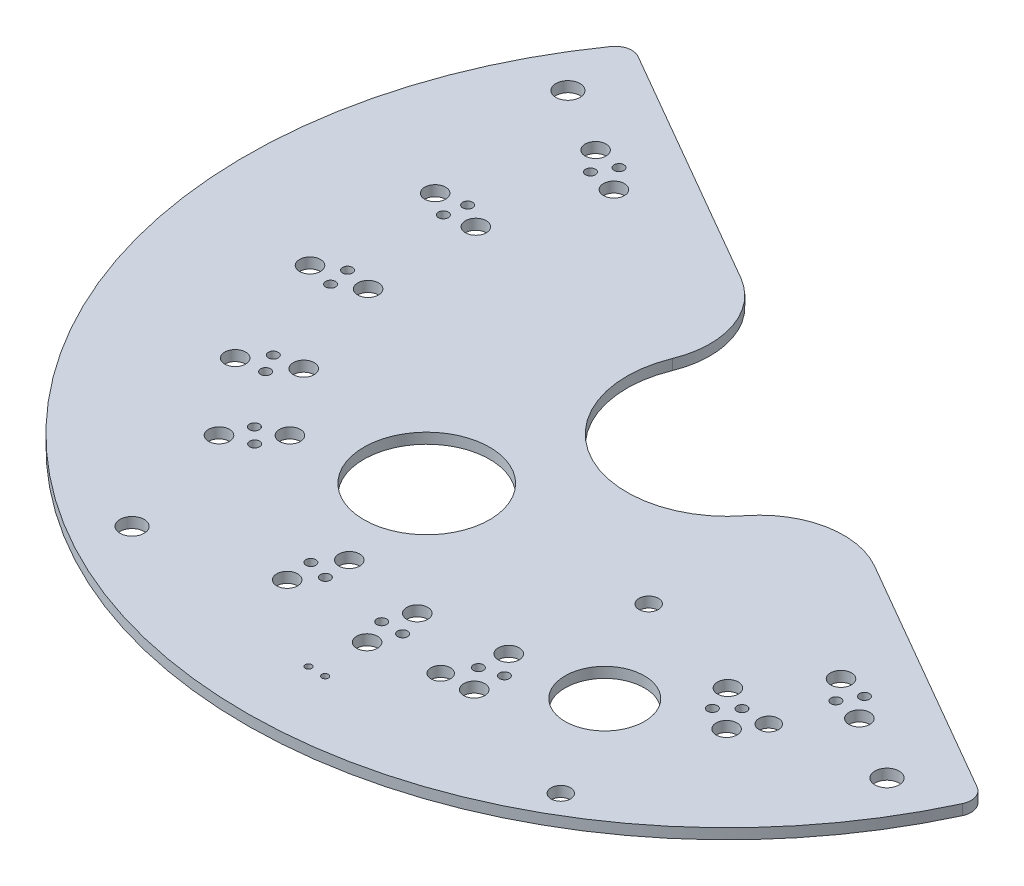
SolidWorks part; units mm, degrees
ref_plane "Front Plane" through (0, 0, 0) normal (0, 0, 1) x (1, 0, 0)
ref_plane "Top Plane" through (0, 0, 0) normal (0, 1, 0) x (1, 0, 0)
ref_plane "Right Plane" through (0, 0, 0) normal (1, 0, 0) x (0, 0, -1)
sketch "Sketch1" plane through (0, 0, 0) normal (0, 1, 0) x (1, 0, 0)
  line L0 (0, 50.8) -> (0, 59.6199) construction
  line L1 (0, 50.8) -> (11.3081, 50.8) construction
  line L2 (0, 0) -> (0, 47) construction
  line L3 (0, 0) -> (-46.286, 8.1615) construction
  line L4 (0, 0) -> (0, 47) construction
  line L5 (0, 0) -> (-46.286, -8.1615) construction
  line L6 (-35.6665, -35.9809) -> (-43.3836, -40.2586) construction
  line L7 (-13.202, -48.8223) -> (-8.5263, -41.3397) construction
  line L8 (34.9566, -37.7798) -> (30.8142, -29.9892) construction
  line L9 (12.3219, -50.1988) -> (12.3219, -41.3754) construction
  circle A0 centre (0, 0) radius 50.8 construction
  circle A1 centre (0, 0) radius 15.24
  circle A2 centre (0, 0) radius 73.025
  circle A3 centre (0, 50.8) radius 6.3 construction
  circle A4 centre (25.4, 43.9941) radius 6.3 construction
  circle A5 centre (43.9941, 25.4) radius 6.3 construction
  circle A6 centre (50.8, 0) radius 6.3 construction
  circle A7 centre (43.9941, -25.4) radius 6.3 construction
  circle A8 centre (25.4, -43.9941) radius 6.3 construction
  circle A9 centre (0, -50.8) radius 6.3 construction
  circle A10 centre (-25.4, -43.9941) radius 6.3 construction
  circle A11 centre (-43.9941, -25.4) radius 6.3 construction
  circle A12 centre (-50.8, 0) radius 6.3 construction
  circle A13 centre (-43.9941, 25.4) radius 6.3 construction
  circle A14 centre (-25.4, 43.9941) radius 6.3 construction
  circle A15 centre (0, 50.8) radius 1.585 construction
  circle A16 centre (-1.585, 50.8) radius 0.75
  circle A17 centre (1.585, 50.8) radius 0.75
  circle A18 centre (0, 50.8) radius 3.8 construction
  circle A19 centre (0, 54.6) radius 1.585
  circle A20 centre (0, 47) radius 1.585
  circle A21 centre (47.285, 27.3) radius 1.585
  circle A22 centre (43.2016, 26.7727) radius 0.75
  circle A23 centre (44.7866, 24.0273) radius 0.75
  circle A24 centre (40.7032, 23.5) radius 1.585
  circle A25 centre (47.285, -27.3) radius 1.585
  circle A26 centre (44.7866, -24.0273) radius 0.75
  circle A27 centre (43.2016, -26.7727) radius 0.75
  circle A28 centre (40.7032, -23.5) radius 1.585
  circle A29 centre (0, -54.6) radius 1.585
  circle A30 centre (1.585, -50.8) radius 0.75
  circle A31 centre (-1.585, -50.8) radius 0.75
  circle A32 centre (0, -47) radius 1.585
  circle A33 centre (-47.285, -27.3) radius 1.585
  circle A34 centre (-43.2016, -26.7727) radius 0.75
  circle A35 centre (-44.7866, -24.0273) radius 0.75
  circle A36 centre (-40.7032, -23.5) radius 1.585
  circle A37 centre (-47.285, 27.3) radius 1.585
  circle A38 centre (-44.7866, 24.0273) radius 0.75
  circle A39 centre (-43.2016, 26.7727) radius 0.75
  circle A40 centre (-40.7032, 23.5) radius 1.585
  circle A41 centre (25.4, 43.9941) radius 20
  circle A42 centre (-16.3207, -29.2429) radius 9.525
  circle A43 centre (25.4, -43.9941) radius 6
  circle A44 centre (-46.286, 8.1615) radius 1.585
  circle A45 centre (-50.3035, 7.2604) radius 0.75
  circle A46 centre (-49.753, 10.3822) radius 0.75
  circle A47 centre (-53.7705, 9.4812) radius 1.585
  circle A48 centre (-46.286, -8.1615) radius 1.585
  circle A49 centre (-49.753, -10.3822) radius 0.75
  circle A50 centre (-50.3035, -7.2604) radius 0.75
  circle A51 centre (-53.7705, -9.4812) radius 1.585
  circle A52 centre (-35.6625, -35.9801) radius 6.3 construction
  circle A53 centre (-35.6625, -35.9801) radius 1.585 construction
  circle A54 centre (-34.5403, -37.1015) radius 0.75
  circle A55 centre (-36.7991, -34.8717) radius 0.75
  circle A56 centre (-35.6625, -35.9801) radius 3.8 construction
  circle A57 centre (-38.371, -38.6691) radius 1.585
  circle A58 centre (-32.9869, -33.3052) radius 1.585
  circle A59 centre (-13.2051, -48.8249) radius 6.3 construction
  circle A60 centre (-13.2051, -48.8249) radius 1.585 construction
  circle A61 centre (-14.7302, -48.3882) radius 0.75
  circle A62 centre (-11.6736, -49.2433) radius 0.75
  circle A63 centre (-13.2051, -48.8249) radius 3.8 construction
  circle A64 centre (-12.1398, -45.16) radius 1.585
  circle A65 centre (-14.2484, -52.4617) radius 1.585
  circle A66 centre (35.9794, -36.0227) radius 6.3 construction
  circle A67 centre (35.9794, -36.0227) radius 1.585 construction
  circle A68 centre (34.8386, -37.1251) radius 0.75
  circle A69 centre (37.1074, -34.9056) radius 0.75
  circle A70 centre (35.9794, -36.0227) radius 3.8 construction
  circle A71 centre (33.3381, -33.2676) radius 1.585
  circle A72 centre (38.6072, -38.7446) radius 1.585
  circle A73 centre (13.281, -49.0556) radius 6.3 construction
  circle A74 centre (13.281, -49.0556) radius 1.585 construction
  circle A75 centre (11.7562, -49.4935) radius 0.75
  circle A76 centre (14.8015, -48.5989) radius 0.75
  circle A77 centre (13.281, -49.0556) radius 3.8 construction
  circle A78 centre (12.2423, -45.3831) radius 1.585
  circle A79 centre (14.3234, -52.6926) radius 1.585
  point P50 (0, 0)
  point P84 (0, 0)
  dimension "D1" = 12
  dimension "D2" = 101.6
  dimension "D3" = 3.17
  dimension "D4" = 1.5
  dimension "D5" = 7.6
  dimension "D6" = 6
  dimension "D7" = 3.17
  dimension "D8" = 40
  dimension "D9" = 19.05
  dimension "D10" = 12
  dimension "D11" = 146.05
  dimension "D12" = 30.48
  dimension "D14" = 80
  dimension "D16" = 100
  dimension "D13" = 2
  dimension "D15" = 2
extrude "Boss-Extrude1" add sketch "Sketch1" against normal blind 1.5875
sketch "Sketch2" plane through (0, 0, 0) normal (0, 1, 0) x (1, 0, 0)
  line L0 (0, 0) -> (0, 66.04) construction
  line L1 (0, 0) -> (-57.1923, 33.02) construction
  circle A0 centre (0, 0) radius 66.04 construction
  circle A1 centre (0, 66.04) radius 1.8288 construction
  circle A2 centre (-57.1923, 33.02) radius 1.8288
  circle A3 centre (33.02, 57.1923) radius 1.8288
  circle A4 centre (57.1923, -33.02) radius 1.8288
  circle A5 centre (-33.02, -57.1923) radius 1.8288
  point P17 (0, 0)
  dimension "D1" = 132.08
  dimension "D2" = 3.6576
  dimension "D3" = 2
  dimension "D4" = 60
  dimension "D5" = 4
extrude "Cut-Extrude1" cut sketch "Sketch2" against normal through all
sketch "Sketch3" plane through (0, 0, 0) normal (0, 1, 0) x (1, 0, 0)
  line L0 (-57.1923, 33.02) -> (57.1923, -33.02) construction
  line L1 (-59.5338, 44.6372) -> (68.4238, -29.2392)
  line L2 (-52.7473, 40.719) -> (61.6373, -25.321) construction
  arc A0 (68.4238, -29.2392) -> (-59.5338, 44.6372) centre (0, 0) ccw
  dimension "D1" = 8.89
extrude "Cut-Extrude2" cut sketch "Sketch3" against normal through all
fillet "Fillet1" radius 12.7 2 edges at (15.165, -0.7937, -1.5098) (-6.275, -0.7937, -13.8882)
fillet "Fillet2" radius 2.54 2 edges at (67.2161, -0.7937, 28.542) (-58.3261, -0.7937, -43.9399)
sketch "Sketch4" plane through (0, 0, 0) normal (0, 1, 0) x (1, 0, 0)
  line L0 (0, 0) -> (0, -73.025) construction
  arc A0 (-59.6949, 42.0615) -> (66.2738, -30.6666) centre (0, 0) ccw construction
  circle A1 centre (0, 0) radius 62.23 construction
  circle A2 centre (0, -62.23) radius 0.4953 construction
  circle A3 centre (1.27, -62.23) radius 0.4953
  circle A4 centre (-1.27, -62.23) radius 0.4953
  dimension "D1" = 0.9906
  dimension "D4" = 124.46
  dimension "D2" = 2
  dimension "D3" = 2
extrude "Cut-Extrude3" cut sketch "Sketch4" against normal through all
sketch "Sketch5" plane through (0, -1.5875, 0) normal (0, -1, 0) x (1, 0, 0)
  line L0 (34.4211, 15.231) -> (45.1187, 21.3934)
  line L1 (-38.2971, 31.6014) -> (-48.2911, 37.8904)
  line L2 (-30.0652, -20.8147) -> (-29.5513, -21.704)
  line L3 (-8.0889, 49.009) -> (-10.353, 60.5023)
  line L4 (-41.5359, 31.0198) -> (-49.3551, 36.4937)
  line L6 (-6.096, 51.4811) -> (-7.5919, 60.9104)
  line L8 (-29.8352, -23.5566) -> (-22.3061, -19.4834)
  line L9 (-31.0536, -21.3854) -> (-35.9288, -24.0498)
  line L10 (-29.8352, -23.5566) -> (-36.3971, -27.1309)
  line L11 (-35.9288, -24.0498) -> (-36.5041, -23.022)
  line L12 (-36.3971, -27.1309) -> (-39.4597, -21.5215)
  line L13 (33.3365, 26.1699) -> (41.5359, 31.0198)
  line L14 (28.0125, 9.134) -> (57.4422, 26.1252)
  line L15 (-44.2736, 0.0193) -> (-49.7418, -0.0511)
  line L16 (-41.9942, 2.6626) -> (-49.6636, 2.6023)
  line L29 (46.7892, 22.3211) -> (55.0735, 27.104)
  line L30 (29.0015, 12.1089) -> (33.4313, 14.6608)
  line L31 (6.096, 41.9407) -> (6.096, 51.4811)
  line L32 (32.4766, 23.8198) -> (41.0187, 28.4067)
  line L34 (3.9949, 40.0768) -> (3.9949, 49.6459)
  line L93 (-25.0455, -19.0828) -> (-29.5513, -21.704)
  arc A0 (1.2876, 63.091) -> (1.2524, 61.369) centre (1.27, 62.23) ccw
  arc A1 (-0.0916, 61.3817) -> (-0.1106, 63.1041) centre (-1.27, 62.23) ccw
  arc A2 (-0.0916, 61.3817) -> (-7.5919, 60.9104) centre (0, 0) ccw
  arc A3 (-0.1106, 63.1041) -> (-54.4738, -31.855) centre (0, 0) ccw
  arc A4 (55.0735, 27.104) -> (1.2524, 61.369) centre (0, 0) ccw
  arc A5 (-43.655, -27.959) -> (-54.1453, -28.9137) centre (-49.1018, -26.2204) cw
  arc A6 (6.096, 51.4811) -> (2.3857, 51.7858) centre (0, 0) ccw
  arc A7 (32.4766, 23.8198) -> (3.9949, 40.0768) centre (0, 0) ccw
  arc A8 (2.3857, 51.7858) -> (2.2966, 49.7481) centre (1.585, 50.8) ccw
  arc A9 (-2.1071, 49.6423) -> (-2.3857, 51.7858) centre (-1.585, 50.8) ccw
  arc A10 (-48.5842, -10.8789) -> (-50.5848, -11.342) centre (-49.753, -10.3822) ccw
  arc A11 (-51.4133, -6.6431) -> (-49.352, -6.4192) centre (-50.3035, -7.2604) ccw
  arc A12 (46.0407, 23.8268) -> (44.4082, 22.815) centre (44.7866, 24.0273) ccw
  arc A13 (41.9556, 27.0186) -> (43.655, 27.959) centre (43.2016, 26.7727) ccw
  arc A14 (-49.292, 6.4925) -> (-51.4133, 6.6431) centre (-50.3035, 7.2604) ccw
  arc A15 (-50.5848, 11.342) -> (-48.5315, 10.7297) centre (-49.753, 10.3822) ccw
  arc A16 (57.4422, 26.1252) -> (1.2876, 63.091) centre (0, 0) ccw
  arc A17 (-2.3857, 51.7858) -> (-6.096, 51.4811) centre (0, 0) ccw
  arc A18 (-2.1071, 49.6423) -> (-8.0889, 49.009) centre (0.1445, -0.1934) ccw
  arc A19 (45.1187, 21.3934) -> (44.4082, 22.815) centre (0.1445, -0.1934) ccw
  arc A20 (29.0015, 12.1089) -> (-25.0455, -19.0828) centre (4.4592, -7.7862) ccw
  arc A21 (28.0125, 9.134) -> (-22.3061, -19.4834) centre (4.4288, -7.9452) ccw
  arc A22 (46.7892, 22.3211) -> (46.0407, 23.8268) centre (0, 0) ccw
  arc A23 (43.655, 27.959) -> (41.5359, 31.0198) centre (0, 0) ccw
  arc A24 (-46.0407, -23.8268) -> (-44.2976, -22.8553) centre (-44.7866, -24.0273) ccw
  arc A25 (-41.947, -26.9697) -> (-43.655, -27.959) centre (-43.2016, -26.7727) ccw
  arc A26 (41.9556, 27.0186) -> (41.0187, 28.4067) centre (0.1445, -0.1934) ccw
  circle A27 centre (1.27, 62.23) radius 0.4953
  arc A28 (-43.655, 27.959) -> (-41.9455, 26.5853) centre (-43.2016, 26.7727) ccw
  arc A29 (-44.0113, 23.0215) -> (-46.0407, 23.8268) centre (-44.7866, 24.0273) ccw
  circle A30 centre (-1.27, 62.23) radius 0.4953
  arc A31 (-41.947, -26.9697) -> (-54.4738, -31.855) centre (-49.6338, -25.7624) cw
  circle A32 centre (-26.7727, 43.2016) radius 1.27 [skipped]
  circle A33 centre (-24.0273, 44.7866) radius 1.27 [skipped]
  circle A34 centre (24.0273, 44.7866) radius 1.27 [skipped]
  circle A35 centre (26.7727, 43.2016) radius 1.27 [skipped]
  circle A36 centre (50.8, 1.585) radius 1.27 [skipped]
  circle A37 centre (50.8, -1.585) radius 1.27 [skipped]
  circle A38 centre (44.7866, -24.0273) radius 1.27 [skipped]
  circle A39 centre (43.2016, -26.7727) radius 1.27 [skipped]
  circle A40 centre (26.7727, -43.2016) radius 1.27 [skipped]
  circle A41 centre (24.0273, -44.7866) radius 1.27 [skipped]
  circle A42 centre (1.585, -50.8) radius 1.27 [skipped]
  circle A43 centre (-1.585, -50.8) radius 1.27 [skipped]
  circle A44 centre (-24.0273, -44.7866) radius 1.27 [skipped]
  circle A45 centre (-26.7727, -43.2016) radius 1.27 [skipped]
  circle A46 centre (-50.8, 1.585) radius 1.27 [skipped]
  circle A47 centre (-50.8, -1.585) radius 1.27 [skipped]
  arc A48 (-39.4597, -21.5215) -> (-44.2736, 0.0193) centre (-4.3951, -2.377) cw
  arc A49 (-38.2971, 31.6014) -> (-41.9455, 26.5853) centre (0.1445, -0.1934) ccw
  arc A50 (33.3365, 26.1699) -> (6.096, 41.9407) centre (0, 0) ccw
  circle A51 centre (1.585, 50.8) radius 0.75
  arc A52 (-46.0407, 23.8268) -> (-47.6319, 20.4612) centre (0, 0) ccw
  arc A53 (3.9949, 49.6459) -> (2.2966, 49.7481) centre (0.1445, -0.1934) ccw
  arc A54 (-41.5359, 31.0198) -> (-43.655, 27.959) centre (0, 0) ccw
  arc A55 (-10.353, 60.5023) -> (-48.2911, 37.8904) centre (0, 0) ccw
  arc A57 (-44.0113, 23.0215) -> (-48.5315, 10.7297) centre (0.1445, -0.1934) ccw
  circle A58 centre (-1.585, 50.8) radius 0.75
  circle A59 centre (43.2016, 26.7727) radius 0.75
  arc A60 (-47.6319, 20.4612) -> (-50.5848, 11.342) centre (0, 0) ccw
  arc A61 (-51.4133, 6.6431) -> (-51.4133, -6.6431) centre (0, 0) ccw
  arc A62 (-49.292, 6.4925) -> (-49.6636, 2.6023) centre (0.1445, -0.1934) ccw
  circle A63 centre (44.7866, 24.0273) radius 0.75
  arc A64 (-50.5848, -11.342) -> (-46.0407, -23.8268) centre (0, 0) ccw
  arc A65 (-48.5842, -10.8789) -> (-44.2976, -22.8553) centre (0.1445, -0.1934) ccw
  circle A66 centre (-43.2016, 26.7727) radius 0.75
  circle A67 centre (-44.7866, 24.0273) radius 0.75
  circle A68 centre (-49.753, 10.3822) radius 0.75
  circle A69 centre (-50.3035, 7.2604) radius 0.75
  circle A70 centre (-50.3035, -7.2604) radius 0.75
  circle A71 centre (-49.753, -10.3822) radius 0.75
  circle A72 centre (-44.7866, -24.0273) radius 0.75
  circle A73 centre (-43.2016, -26.7727) radius 0.75
  arc A74 (29.7503, 20.2948) -> (30.8424, 21.1896) centre (30.9918, 19.8934) ccw construction
  arc A75 (4.5236, 34.6192) -> (30.8424, 21.1896) centre (5.7054, 4.4312) cw construction
  arc A76 (4.4841, 33.194) -> (29.7503, 20.2948) centre (4.8534, 2.7227) cw construction
  arc A77 (33.6777, 16.7261) -> (32.7717, 15.8021) centre (32.4444, 17.0292) ccw
  arc A78 (33.4313, 14.6608) -> (32.7717, 15.8021) centre (-10.0197, -9.6891) ccw
  arc A79 (34.4211, 15.231) -> (33.6777, 16.7261) centre (-12.363, -7.1008) ccw
  arc A80 (-0.8928, 32.9745) -> (-0.4432, 34.9562) centre (0.075, 33.7967) ccw construction
  arc A81 (-29.697, 19.0828) -> (-24.1699, 25.0755) centre (2.1808, -4.7732) cw construction
  arc A82 (4.5236, 34.6192) -> (4.4841, 33.194) centre (3.4532, 33.9357) ccw construction
  circle A83 centre (-31.1738, -20.0389) radius 0.75
  arc A84 (-29.697, 19.0828) -> (-28.1584, 17.7555) centre (-29.4254, 17.8422) ccw construction
  arc A85 (-28.1584, 17.7555) -> (-0.8928, 32.9745) centre (0.881, -2.2367) cw construction
  arc A86 (-31.3368, 13.0383) -> (-32.985, 14.2011) centre (-31.3367, 14.7878) ccw construction
  arc A87 (-32.985, 14.2011) -> (-34.3304, 11.6344) centre (112.8254, -63.8668) ccw construction
  arc A88 (-33.9153, -16.8172) -> (-31.9293, -16.3872) centre (-32.7611, -17.3469) ccw construction
  arc A89 (-31.9293, -16.3872) -> (-32.6415, -14.9048) centre (-79.0072, -38.0929) ccw construction
  arc A90 (-30.0652, -20.8147) -> (-31.0536, -21.3854) centre (-31.1268, -20.1175) ccw
  circle A91 centre (-32.7183, -17.2601) radius 0.75 construction
  arc A92 (-34.3304, 11.6344) -> (-33.9153, -16.8172) centre (-7.3644, -2.2011) ccw construction
  arc A93 (-31.3368, 13.0383) -> (-32.6415, -14.9048) centre (-7.0347, -2.0984) ccw construction
  circle A94 centre (-31.007, 15.1229) radius 0.75 construction
  circle A95 centre (-29.3984, 17.8491) radius 0.75 construction
  circle A96 centre (0.1843, 33.8387) radius 0.75 construction
  circle A97 centre (3.3549, 33.875) radius 0.75 construction
  circle A98 centre (30.9845, 19.7892) radius 0.75 construction
  circle A99 centre (32.5074, 16.9933) radius 0.75
  arc A101 (-49.3551, 36.4937) -> (-54.1453, -28.9137) centre (0, 0) ccw
  arc A103 (-24.1699, 25.0755) -> (-0.4432, 34.9562) centre (2.1808, -4.7732) cw construction
  arc A104 (-36.5041, -23.022) -> (-41.9942, 2.6626) centre (2.3103, -1.2963) cw
  arc A105 (-49.7418, -0.0511) -> (-49.352, -6.4192) centre (0.1445, -0.1934) ccw
  point P34 (0, 0)
  point P36 (0, 0)
  point P82 (0, 0)
  point P125 (0, 0)
  point P126 (-46.9727, 38.6353)
  point P130 (0, 0)
  point P141 (-38.2971, 31.6014)
  point P142 (-47.7865, 38.7316)
  point P147 (-48.2911, 37.8904)
  dimension "D13" = 12
  dimension "D15" = 3
extrude "Boss-Extrude2" add sketch "Sketch5" along normal blind 0.1016
sketch "Sketch6" plane through (0, -1.5875, 0) normal (0, -1, 0) x (1, 0, 0)
  line L0 (0, 0) -> (25.4, 43.9941) construction
  line L1 (25.4, 43.9941) -> (36.5125, 63.2415) construction
  circle A0 centre (25.4, 43.9941) radius 18.1937 construction
  arc A1 (66.2738, 30.6666) -> (-59.6949, -42.0615) centre (0, 0) ccw construction
  circle A2 centre (34.4969, 59.7503) radius 1.4732
  circle A3 centre (9.6438, 53.0909) radius 1.4732
  circle A4 centre (16.3031, 28.2379) radius 1.4732
  circle A5 centre (41.1562, 34.8972) radius 1.4732
  point P20 (25.4, 43.9941)
  dimension "D1" = 2.9464
extrude "Cut-Extrude4" cut sketch "Sketch6" against normal through all
